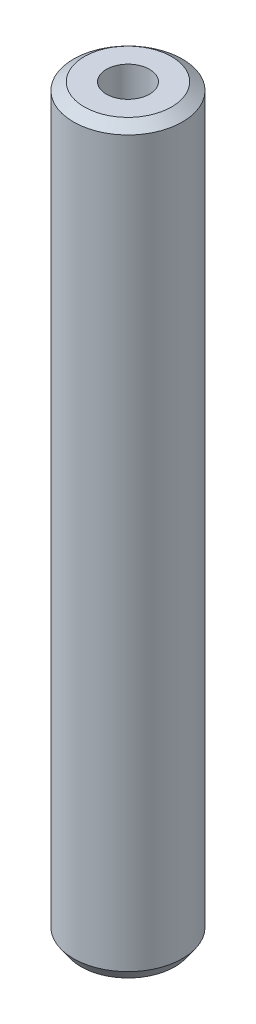
SolidWorks part; units mm, degrees
ref_plane "Front Plane" through (0, 0, 0) normal (0, 0, 1) x (1, 0, 0)
ref_plane "Top Plane" through (0, 0, 0) normal (0, 1, 0) x (1, 0, 0)
ref_plane "Right Plane" through (0, 0, 0) normal (1, 0, 0) x (0, 0, -1)
sketch "Sketch1" plane through (0, 0, 0) normal (0, 1, 0) x (1, 0, 0)
  circle A0 centre (0, 0) radius 20
  dimension "SHAFT_OD" = 40
extrude "Boss-Extrude1" add sketch "Sketch1" along normal blind 272.646
sketch "Sketch2" plane through (0, 0, 0) normal (0, 1, 0) x (1, 0, 0)
  circle A0 centre (0, 0) radius 7.9127
  dimension "BORE_D" = 15.8255
extrude "Cut-Extrude1" cut sketch "Sketch2" along normal through all
chamfer "Chamfer1" distance 2.7817 angle 55.066 2 edges at (0, 272.646, 20) (0, 0, 20) first distance on face at (0, 272.646, 20) first distance on face at (0, 0, 7.9127)
